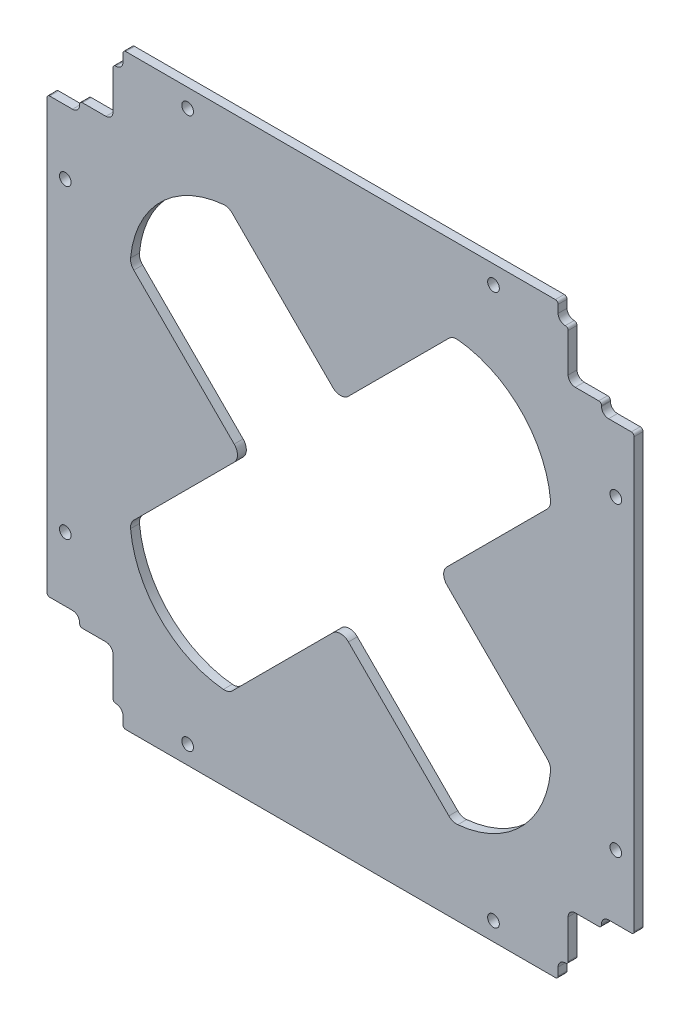
SolidWorks part; units mm, degrees
material "FR4_stuffedProtoboard"
ref_plane "Front Plane" through (0, 0, 0) normal (0, 0, 1) x (1, 0, 0)
ref_plane "Top Plane" through (0, 0, 0) normal (0, 1, 0) x (1, 0, 0)
ref_plane "Right Plane" through (0, 0, 0) normal (1, 0, 0) x (0, 0, -1)
sketch "Sketch1" plane through (0, 0, 0) normal (0, 0, 1) x (1, 0, 0)
  line L0 (53, 53) -> (-53, -53) construction
  line L1 (53, 53) -> (-53, 53)
  line L2 (53, 53) -> (53, -53)
  line L3 (53, -53) -> (-53, -53)
  line L4 (-53, 53) -> (-53, -53)
  point P4 (0, 0)
  dimension "D1" = 106
  dimension "D2" = 106
extrude "mainOutline" add sketch "Sketch1" along normal blind 1.6
sketch "axisLabels" plane through (0, 0, 0) normal (0, 0, -1) x (-1, 0, 0)
  text T0 "+Y"
  text T1 "+X"
sketch "Sketch4" plane through (0, 0, 0) normal (0, 0, -1) x (-1, 0, 0)
  line L10 (-53, 53) -> (53, 53) construction
  line L29 (41.3, 53) -> (41.3, 41.3)
  line L31 (53, 41.3) -> (41.3, 41.3)
  line L46 (53, 53) -> (53, -53) construction
  line L51 (53, 41.3) -> (53, 53)
  line L52 (53, 53) -> (41.3, 53)
  dimension "D11" = 11.7
  dimension "D12" = 11.7
extrude "railCutouts" cut sketch "Sketch4" against normal through all
sketch "Sketch13" plane through (0, 0, 0) normal (0, 0, -1) x (-1, 0, 0)
  line L0 (47.3, 39.4) -> (47.3, 41.3)
  line L2 (53, 41.3) -> (53, 39.4)
  line L5 (41.3, 53) -> (39.5, 53)
  line L6 (41.3, 53) -> (41.3, 50)
  line L7 (41.3, 50) -> (39.5, 50)
  line L8 (39.5, 53) -> (39.5, 50)
  line L9 (53, 41.3) -> (53, -53) construction
  line L10 (53, 41.3) -> (47.3, 41.3)
  line L12 (53, 39.4) -> (47.3, 39.4)
  line L13 (41.3, 41.3) -> (53, 41.3) construction
  dimension "D1" = 5.7
  dimension "D3" = 1.9
  dimension "D5" = 1.8
  dimension "D6" = 3
extrude "filletCutouts" cut sketch "Sketch13" against normal through all both and the other way through all
sketch "Sketch5" plane through (0, 0, 0) normal (0, 0, -1) x (-1, 0, 0)
  line L23 (42.198, 42.198) -> (45.4803, 45.4803) construction
  line L24 (41.3, 43.0961) -> (44.5823, 46.3784)
  line L25 (43.0961, 41.3) -> (46.3784, 44.5823)
  line L41 (41.3, 50) -> (41.3, 41.3) construction
  arc A14 (41.3, 43.0961) -> (43.0961, 41.3) centre (42.198, 42.198) ccw
  arc A15 (46.3784, 44.5823) -> (44.5823, 46.3784) centre (45.4803, 45.4803) ccw
  point P0 (41.3, 41.3)
  point P52 (43.8392, 43.8392)
  dimension "D14" = 1.27
  dimension "D7" = 45
extrude "dogbone" [suppressed] cut sketch "Sketch5" against normal through all
sketch "Sketch14" plane through (0, 0, 1.6) normal (0, 0, 1) x (1, 0, 0)
  point P1 (-47.3, 39.4)
sketch "Sketch27" plane through (0, 0, 1.6) normal (0, 0, 1) x (1, 0, 0)
  line L0 (-40.928, 42.198) -> (-40.928, 49.628)
  line L1 (-48.198, 39.028) -> (-53, 39.028)
  line L2 (-53, 39.4) -> (-53, -53) construction
  line L3 (-53, 39.028) -> (-53, 53)
  line L4 (-53, 53) -> (-39.128, 53)
  line L5 (-39.128, 53) -> (-39.128, 50.898)
  line L6 (-40.928, 49.628) -> (-40.398, 49.628)
  line L7 (-42.198, 40.928) -> (-46.928, 40.928)
  line L8 (-46.928, 40.928) -> (-46.928, 40.298)
  line L10 (53, 53) -> (-39.5, 53) construction
  arc A0 (-42.198, 40.928) -> (-40.928, 42.198) centre (-42.198, 42.198) ccw
  arc A1 (-40.398, 49.628) -> (-39.128, 50.898) centre (-40.398, 50.898) ccw
  arc A2 (-48.198, 39.028) -> (-46.928, 40.298) centre (-48.198, 40.298) ccw
  dimension "D1" = 1.27
extrude "smoothCorner" cut sketch "Sketch27" against normal blind 10
pattern_sketch "Sketch-Pattern1" [suppressed] of bodies 103 driven by "Sketch14"
mirror "Mirror1" about plane through (0, 0, 0) normal (1, 0, 0) of "smoothCorner", "filletCutouts", "railCutouts"
mirror "Mirror2" about plane through (0, 0, 0) normal (0, 1, 0) of "Mirror1"
fillet "Fillet1" [suppressed] radius 0.5
fillet "Fillet10" radius 0.5 8 edges at (46.928, -40.928, 0.8) (40.928, -49.628, 0.8) (40.928, 49.628, 0.8) (46.928, 40.928, 0.8) (-46.928, 40.928, 0.8) (-40.928, 49.628, 0.8) (-46.928, -40.928, 0.8) (-40.928, -49.628, 0.8)
sketch "Sketch6" [suppressed] plane through (0, 0, 0) normal (0, 0, -1) x (-1, 0, 0)
  line L0 (-39, 50) -> (-39, 53) construction
  line L1 (-39, 49) -> (-39, 53) construction
  line L2 (-53, 53) -> (41.3, 53) construction
  line L3 (-40, 50) -> (-40, 53)
  line L4 (-38, 50) -> (-38, 53)
  line L5 (-49, 39) -> (-53, 39) construction
  line L6 (-53, 39) -> (-48, 39) construction
  line L7 (-49, 38) -> (-53, 38)
  line L8 (-49, 40) -> (-53, 40)
  line L9 (-49, -39) -> (-55.2142, -39) construction
  line L10 (-48, -39) -> (-53, -39) construction
  line L11 (-49, -40) -> (-55.2142, -40)
  line L12 (-49, -38) -> (-55.2142, -38)
  line L13 (-39, -50) -> (-39, -53.9161) construction
  line L14 (-39, -53) -> (-39, -49) construction
  line L15 (-38, -50) -> (-38, -53.9161)
  line L16 (-40, -50) -> (-40, -53.9161)
  line L17 (39, -50.9) -> (39, -54.538) construction
  line L18 (39, -49.9) -> (39, -53) construction
  line L19 (40, -50.9) -> (40, -54.538)
  line L20 (38, -50.9) -> (38, -54.538)
  line L21 (49, -40.5) -> (54.2026, -40.5) construction
  line L22 (53, -40.5) -> (48, -40.5) construction
  line L23 (49, -39.5) -> (54.2026, -39.5)
  line L24 (49, -41.5) -> (54.2026, -41.5)
  line L25 (49, 40.5) -> (54.5566, 40.5) construction
  line L26 (48, 40.5) -> (53, 40.5) construction
  line L27 (49, 41.5) -> (54.5566, 41.5)
  line L28 (49, 39.5) -> (54.5566, 39.5)
  line L29 (39, 50.9) -> (39, 55.8281) construction
  line L30 (39, 53) -> (39, 49.9) construction
  line L31 (38, 50.9) -> (38, 55.8281)
  line L32 (40, 50.9) -> (40, 55.8281)
  line L33 (-48, -41.4) -> (-48, -39) construction
  line L34 (-39, -49) -> (-41.4, -49) construction
  line L35 (41.4, -49.9) -> (39, -49.9) construction
  line L36 (48, -40.5) -> (48, -41.4) construction
  line L37 (48, 41.4) -> (48, 40.5) construction
  line L38 (39, 49.9) -> (41.4, 49.9) construction
  arc A0 (-40, 50) -> (-38, 50) centre (-39, 50) ccw
  arc A1 (-38, 53) -> (-40, 53) centre (-39, 53) ccw
  arc A2 (-49, 38) -> (-49, 40) centre (-49, 39) ccw
  arc A3 (-53, 40) -> (-53, 38) centre (-53, 39) ccw
  arc A4 (-49, -40) -> (-49, -38) centre (-49, -39) ccw
  arc A5 (-55.2142, -38) -> (-55.2142, -40) centre (-55.2142, -39) ccw
  arc A6 (-38, -50) -> (-40, -50) centre (-39, -50) ccw
  arc A7 (-40, -53.9161) -> (-38, -53.9161) centre (-39, -53.9161) ccw
  arc A8 (40, -50.9) -> (38, -50.9) centre (39, -50.9) ccw
  arc A9 (38, -54.538) -> (40, -54.538) centre (39, -54.538) ccw
  arc A10 (49, -39.5) -> (49, -41.5) centre (49, -40.5) ccw
  arc A11 (54.2026, -41.5) -> (54.2026, -39.5) centre (54.2026, -40.5) ccw
  arc A12 (49, 41.5) -> (49, 39.5) centre (49, 40.5) ccw
  arc A13 (54.5566, 39.5) -> (54.5566, 41.5) centre (54.5566, 40.5) ccw
  arc A14 (38, 50.9) -> (40, 50.9) centre (39, 50.9) ccw
  arc A15 (40, 55.8281) -> (38, 55.8281) centre (39, 55.8281) ccw
  point P6 (-39, 51.5)
  point P11 (-51, 39)
  point P21 (-52.1071, -39)
  point P30 (-39, -51.958)
  point P39 (39, -52.719)
  point P48 (51.6013, -40.5)
  point P57 (51.7783, 40.5)
  point P66 (39, 53.364)
  point P75 (-39, 49)
  dimension "D1" = 1
extrude "solarFillets" [suppressed] cut sketch "Sketch6" against normal through all
fillet "handlingFillets" [suppressed] radius 1
sketch "Sketch7" plane through (0, 0, 1.6) normal (0, 0, 1) x (1, 0, 0)
  line L0 (-39.128, -53) -> (39.128, -53) construction
  line L1 (-53, 39.028) -> (-53, -39.028) construction
  line L2 (39.128, 53) -> (-39.128, 53) construction
  line L3 (-31.37, 28.67) -> (-31.37, 31.21) construction
  line L4 (-31.37, 31.21) -> (-28.83, 31.21) construction
  line L5 (-28.83, 31.21) -> (-28.83, 28.67) construction
  line L6 (-28.83, 28.67) -> (-31.37, 28.67) construction
  line L7 (-31.37, 28.67) -> (-28.83, 31.21) construction
  circle A1 centre (-28.4723, -17.925) radius 0.8
  circle A3 centre (-28.4723, -33.775) radius 0.8
  circle A5 centre (-31.37, 28.67) radius 0.425
  circle A7 centre (-28.83, 28.67) radius 0.425
  circle A9 centre (-30.1, 29.94) radius 0.425
  circle A10 centre (-28.83, 31.21) radius 0.425
  circle A11 centre (-31.37, 31.21) radius 0.425
  circle A12 centre (-31.37, 21.27) radius 0.425
  circle A13 centre (-28.83, 21.27) radius 0.425
  circle A14 centre (-30.1, 22.54) radius 0.425
  circle A15 centre (-28.83, 23.81) radius 0.425
  circle A16 centre (-31.37, 23.81) radius 0.425
  circle A17 centre (-31.37, 13.87) radius 0.425
  circle A18 centre (-28.83, 13.87) radius 0.425
  circle A19 centre (-30.1, 15.14) radius 0.425
  circle A20 centre (-28.83, 16.41) radius 0.425
  circle A21 centre (-31.37, 16.41) radius 0.425
  point P13 (-30.1, 29.94)
  dimension "D8" = 1.6
  dimension "D9" = 3
  dimension "D6" = 0.85
  dimension "D1" = 19.225
  dimension "D2" = 24.5277
  dimension "D3" = 15.85
  dimension "D4" = 23.06
  dimension "D5" = 22.9
  dimension "D7" = 2.54
  dimension "D10" = 7.4
extrude "connectorHoles" [suppressed] cut sketch "Sketch7" against normal through all
hole_wizard "M2 Clearance Hole1" positions "Sketch8" profile "Sketch9" hole size "M2" standard "ANSI Metric" end condition through all
sketch "Sketch8" plane through (0, 0, 0) normal (0, 0, -1) x (-1, 0, 0)
  line L0 (53, 39.028) -> (53, -39.028) construction
  line L1 (39.128, -53) -> (-39.128, -53) construction
  line L2 (-53, -39.028) -> (-53, 39.028) construction
  line L3 (53, 0) -> (-53, 0) construction
  line L5 (0, -53) -> (0, -11.6379) construction
  line L6 (53, 39.028) -> (53, -39.028) construction
  point P0 (49.5, -27.5)
  point P1 (27.5, -49.5)
  point P5 (-49.5, -27.5)
  point P30 (-27.5, -49.5)
  point P31 (-27.5, 49.5)
  point P32 (-49.5, 27.5)
  point P33 (27.5, 49.5)
  point P34 (49.5, 27.5)
  dimension "D1" = 3.5
  dimension "D2" = 3.5
  dimension "D3" = 55
  dimension "D4" = 3.5
  dimension "D5" = 55
  dimension "D6" = 55
sketch "Sketch9" plane through (-49.5, -27.5, 0) normal (1, 0, 0) x (0, 1, 0)
  line L0 (0, 0) -> (0, 1.6)
  line L1 (0, 1.6) -> (1.05, 1.6)
  line L2 (1.05, 1.6) -> (1.05, 0)
  line L5 (1.05, 0) -> (0, 0)
  line L11 (0, -6.35) -> (0, 107.95) construction
  dimension "Thru Hole Dia." = 2.1
  dimension "Thru Hole Depth" = 1.6
sketch "Sketch12" plane through (0, 0, 1.6) normal (0, 0, 1) x (1, 0, 0)
  line L1 (-39.128, -53) -> (39.128, -53) construction
  line L2 (53, -39.028) -> (53, 39.028) construction
  circle A0 centre (27.815, -42.5) radius 0.8
  circle A1 centre (38.585, -42.5) radius 0.8
  dimension "D1" = 1.6
  dimension "D2" = 10.77
  dimension "D3" = 10.5
  dimension "D4" = 25.185
extrude "interboardConnectorHoles" [suppressed] cut sketch "Sketch12" against normal through all both and the other way through all
sketch "Sketch17" [suppressed] plane through (0, 0, 1.6) normal (0, 0, 1) x (1, 0, 0)
  line L1 (-35.8, -40) -> (-21.8, -40)
  line L2 (-35.8, -40) -> (-35.8, -45)
  line L3 (-35.8, -45) -> (-21.8, -45)
  line L4 (-21.8, -40) -> (-21.8, -45)
  line L5 (-41.3, -50) -> (-41.3, -43.2836) construction
  line L6 (-38.9, -53) -> (38.9, -53) construction
  dimension "D1" = 8
  dimension "D2" = 13
  dimension "D3" = 19.5
  dimension "D4" = 14
  dimension "D5" = 5.5
extrude "Cut-Extrude7" [suppressed] cut sketch "Sketch17" against normal through all both and the other way through all
fillet "Fillet2" [suppressed] radius 1.27
sketch "Sketch11" [suppressed] plane through (0, 0, 0) normal (0, 0, -1) x (-1, 0, 0)
  circle A0 centre (0, 0) radius 36
  dimension "D1" = 72
extrude "Cut-Extrude2" [suppressed] cut sketch "Sketch11" against normal through all both and the other way through all
sketch "Sketch15" plane through (0, 0, 0) normal (0, 0, -1) x (-1, 0, 0)
  line L0 (-39.128, 53) -> (39.128, 53) construction
  line L1 (45, 53) -> (-45, 53)
  line L2 (45, 53) -> (45, 46.8)
  line L3 (45, 46.8) -> (-45, 46.8)
  line L4 (-45, 53) -> (-45, 46.8)
  line L5 (45, -53) -> (-45, -53)
  line L6 (45, -53) -> (45, -46.8)
  line L7 (45, -46.8) -> (-45, -46.8)
  line L8 (-45, -53) -> (-45, -46.8)
  line L9 (39.128, -53) -> (-39.128, -53) construction
  line L10 (-53, -39.028) -> (-53, 39.028) construction
  line L11 (-53, 45) -> (-47.8, 45)
  line L12 (-53, 45) -> (-53, -45)
  line L13 (-53, -45) -> (-47.8, -45)
  line L14 (-47.8, 45) -> (-47.8, -45)
  line L15 (53, 45) -> (47.8, 45)
  line L16 (53, 45) -> (53, -45)
  line L17 (53, -45) -> (47.8, -45)
  line L18 (47.8, 45) -> (47.8, -45)
  line L19 (53, 39.028) -> (53, -39.028) construction
  point P8 (0, 53)
  point P11 (0, -53)
  point P22 (-53, 0)
  point P25 (53, 0)
  dimension "D1" = 90
  dimension "D3" = 6.2
  dimension "D5" = 5.2
extrude "Cut-Extrude5" cut sketch "Sketch15" against normal blind 0.001
sketch "Sketch18" [suppressed] plane through (0, 0, 1.6) normal (0, 0, 1) x (1, 0, 0)
  line L0 (-43.2836, -41.3) -> (-46.4, -41.3) construction
  line L1 (-44.8418, -41.3) -> (-41.3, -41.3)
  line L2 (-44.8418, -41.3) -> (-44.8418, -36.3)
  line L3 (-44.8418, -36.3) -> (-41.3, -36.3)
  line L4 (-41.3, -41.3) -> (-41.3, -36.3)
  line L5 (-41.3, -50) -> (-41.3, -43.2836) construction
  dimension "D1" = 5
extrude "Boss-Extrude1" [suppressed] add sketch "Sketch18" against normal up to surface (1.6 mm away) up to face at (0, 0, 0)
sketch "Sketch16" [suppressed] plane through (0, 0, 1.6) normal (0, 0, 1) x (1, 0, 0)
  line L4 (-45, -53) -> (45, -53)
  line L5 (45, -53) -> (45, -46.8)
  line L6 (45, -46.8) -> (-45, -46.8)
  line L7 (-45, -46.8) -> (-45, -53)
  line L8 (-45, -53) -> (45, -53)
  line L9 (45, -53) -> (45, -46.8)
  line L10 (45, -46.8) -> (-45, -46.8)
  line L11 (-45, -46.8) -> (-45, -53)
  line L12 (45, 53) -> (-45, 53)
  line L13 (45, 46.8) -> (45, 53)
  line L14 (-45, 46.8) -> (45, 46.8)
  line L15 (-45, 53) -> (-45, 46.8)
  line L16 (45, 53) -> (-45, 53)
  line L17 (45, 46.8) -> (45, 53)
  line L18 (-45, 46.8) -> (45, 46.8)
  line L19 (-45, 53) -> (-45, 46.8)
  line L20 (-47.8, 45) -> (-53, 45)
  line L21 (-53, 45) -> (-53, -45)
  line L22 (-53, -45) -> (-47.8, -45)
  line L23 (-47.8, -45) -> (-47.8, 45)
  line L24 (-47.8, 45) -> (-53, 45)
  line L25 (-53, 45) -> (-53, -45)
  line L26 (-53, -45) -> (-47.8, -45)
  line L27 (-47.8, -45) -> (-47.8, 45)
  line L28 (53, 45) -> (47.8, 45)
  line L29 (47.8, 45) -> (47.8, -45)
  line L30 (47.8, -45) -> (53, -45)
  line L31 (53, -45) -> (53, 45)
  line L32 (53, 45) -> (47.8, 45)
  line L33 (47.8, 45) -> (47.8, -45)
  line L34 (47.8, -45) -> (53, -45)
  line L35 (53, -45) -> (53, 45)
  dimension "D1" = 0
  dimension "D2" = 0
  dimension "D3" = 0
  dimension "D4" = 0
extrude "Cut-Extrude6" [suppressed] cut sketch "Sketch16" against normal blind 0.001
sketch "Sketch19" plane through (0, 0, 0) normal (0, 0, 1) x (1, 0, 0)
  line L50 (14, -4) -> (6, -4) construction
  line L51 (32, -13.5731) -> (32, -10.1269) construction
  line L54 (0, -16.7) -> (0, -7) construction
  line L55 (6, -19.7) -> (14, -19.7) construction
  line L80 (14, -4) -> (6, -4) construction
  line L81 (32, -13.5731) -> (32, -10.1269) construction
  line L89 (0, -16.7) -> (0, -7) construction
  line L90 (6, -19.7) -> (14, -19.7) construction
  line L91 (0, -4) -> (36, -4)
  line L92 (0, -4) -> (0, -19.7)
  line L93 (0, -19.7) -> (36, -19.7)
  line L106 (-1, -3) -> (-1, -20.7)
  line L107 (-1, -20.7) -> (36.6053, -20.7)
  line L108 (-1, -3) -> (36.6053, -3)
  line L109 (-3, 1) -> (-20.7, 1)
  line L110 (-3, 1) -> (-3, -36.6053)
  line L111 (-20.7, 1) -> (-20.7, -36.6053)
  line L112 (1, 3) -> (1, 20.7)
  line L113 (1, 3) -> (-36.6053, 3)
  line L114 (1, 20.7) -> (-36.6053, 20.7)
  line L115 (3, -1) -> (20.7, -1)
  line L116 (3, -1) -> (3, 36.6053)
  line L117 (20.7, -1) -> (20.7, 36.6053)
  arc A9 (36, -4) -> (36, -19.7) centre (20.3594, -11.85) cw
  arc A13 (36.6053, -3) -> (36.6053, -20.7) centre (20.3594, -11.85) cw
  arc A14 (-3, -36.6053) -> (-20.7, -36.6053) centre (-11.85, -20.3594) cw
  arc A15 (-36.6053, 3) -> (-36.6053, 20.7) centre (-20.3594, 11.85) cw
  arc A16 (3, 36.6053) -> (20.7, 36.6053) centre (11.85, 20.3594) cw
  dimension "D1" = 17.5
  dimension "D2" = 36
  dimension "D3" = 1
  dimension "D4" = 4
sketch "Sketch21" plane through (0, 0, 0) normal (0, 0, 1) x (1, 0, 0)
  circle A0 centre (0, 0) radius 22.5
  dimension "D1" = 45
extrude "Cut-Extrude10" [suppressed] cut sketch "Sketch21" against normal through all and the other way through all
sketch "Sketch22" [suppressed] plane through (0, 0, 1.6) normal (0, 0, 1) x (1, 0, 0)
  line L0 (21.5668, -46.3155) -> (46.3155, -21.5668)
  line L1 (38.5373, -13.7886) -> (46.3155, -21.5668) construction
  line L2 (21.5668, -46.3155) -> (-12.3744, -12.3744)
  line L3 (13.7886, -38.5373) -> (38.5373, -13.7886) construction
  line L4 (13.7886, -38.5373) -> (38.5373, -13.7886) construction
  line L5 (-12.3744, -12.3744) -> (12.3744, 12.3744)
  line L6 (12.3744, 12.3744) -> (46.3155, -21.5668)
  dimension "D1" = 11
extrude "Cut-Extrude11" [suppressed] cut sketch "Sketch22" against normal through all both and the other way through all
fillet "Fillet4" [suppressed] radius 2
extrude "1U pinwheel turnstile cutout" [suppressed] cut sketch "Sketch19" along normal up to next contours L111 A14 L110 L109 | L107 A13 L108 L106 | L116 A16 L117 L115 | L112 L114 A15 L113
sketch "Sketch26" plane through (0, 0, 1.6) normal (0, 0, 1) x (1, 0, 0)
  line L0 (-16.2988, 0) -> (-36.8049, 20.5061) construction
  line L1 (0, 16.2988) -> (-7.7782, 24.077) construction
  line L2 (-24.077, 7.7782) -> (-16.2988, 0) construction
  line L3 (0, 16.2988) -> (-7.7782, 24.077) construction
  line L4 (-24.077, 7.7782) -> (-16.2988, 0) construction
  line L5 (-20.5061, 36.8049) -> (0, 16.2988) construction
  line L6 (36.8049, 20.5061) -> (16.2988, 0) construction
  line L7 (0, 16.2988) -> (20.5061, 36.8049) construction
  line L8 (20.5061, -36.8049) -> (0, -16.2988) construction
  line L9 (16.2988, 0) -> (36.8049, -20.5061) construction
  line L10 (-36.8049, -20.5061) -> (-16.2988, 0) construction
  line L11 (0, -16.2988) -> (-20.5061, -36.8049) construction
  line L12 (-17.713, 0) -> (-37.8275, 20.1145)
  line L13 (-20.1145, 37.8275) -> (0, 17.713)
  line L14 (0, 17.713) -> (20.1145, 37.8275)
  line L15 (37.8275, 20.1145) -> (17.713, 0)
  line L16 (17.713, 0) -> (37.8275, -20.1145)
  line L17 (20.1145, -37.8275) -> (0, -17.713)
  line L18 (0, -17.713) -> (-20.1145, -37.8275)
  line L19 (-37.8275, -20.1145) -> (-17.713, 0)
  arc A0 (-17.1196, 32.4741) -> (-32.4741, 17.1196) centre (-16.2012, 16.2012) ccw construction
  arc A1 (-17.1196, 32.4741) -> (-32.4741, 17.1196) centre (-16.2012, 16.2012) ccw construction
  arc A2 (-36.8049, 20.5061) -> (-20.5061, 36.8049) centre (-19.3436, 19.3436) cw construction
  arc A3 (20.5061, 36.8049) -> (36.8049, 20.5061) centre (19.3436, 19.3436) cw construction
  arc A4 (36.8049, -20.5061) -> (20.5061, -36.8049) centre (19.3436, -19.3436) cw construction
  arc A5 (-20.5061, -36.8049) -> (-36.8049, -20.5061) centre (-19.3436, -19.3436) cw construction
  arc A6 (-37.8275, 20.1145) -> (-20.1145, 37.8275) centre (-19.3436, 19.3436) cw
  arc A7 (20.1145, 37.8275) -> (37.8275, 20.1145) centre (19.3436, 19.3436) cw
  arc A8 (37.8275, -20.1145) -> (20.1145, -37.8275) centre (19.3436, -19.3436) cw
  arc A9 (-20.1145, -37.8275) -> (-37.8275, -20.1145) centre (-19.3436, -19.3436) cw
  dimension "D1" = 17.5
  dimension "D3" = 4
  dimension "D2" = 29
  dimension "D4" = 1
extrude "1I circular turnstile cutout" cut sketch "Sketch26" against normal blind 10
sketch "Sketch25" [suppressed] plane through (0, 0, 0) normal (0, 0, -1) x (-1, 0, 0)
  line L0 (36.332, -29.0597) -> (36.332, -25.6135) construction
  line L1 (10.332, -35.1866) -> (18.332, -35.1866) construction
  line L2 (18.332, -19.4866) -> (10.332, -19.4866) construction
  line L3 (4.332, -32.1866) -> (4.332, -22.4866) construction
  line L4 (36.332, -29.0597) -> (36.332, -25.6135) construction
  line L5 (10.332, -35.1866) -> (18.332, -35.1866) construction
  line L6 (18.332, -19.4866) -> (10.332, -19.4866) construction
  line L7 (4.332, -32.1866) -> (4.332, -22.4866) construction
  line L8 (40.332, -35.1866) -> (4.332, -35.1866) construction
  line L9 (4.332, -35.1866) -> (4.332, -19.4866) construction
  line L10 (4.332, -19.4866) -> (40.332, -19.4866) construction
  line L11 (40.9373, -36.1866) -> (3.332, -36.1866)
  line L12 (3.332, -36.1866) -> (3.332, -18.4866)
  line L13 (3.332, -18.4866) -> (40.9373, -18.4866)
  line L14 (-18.4866, -3.332) -> (-18.4866, -40.9373)
  line L15 (-36.1866, -3.332) -> (-18.4866, -3.332)
  line L16 (-36.1866, -40.9373) -> (-36.1866, -3.332)
  line L17 (-3.332, 18.4866) -> (-40.9373, 18.4866)
  line L18 (-3.332, 36.1866) -> (-3.332, 18.4866)
  line L19 (-40.9373, 36.1866) -> (-3.332, 36.1866)
  line L20 (18.4866, 3.332) -> (18.4866, 40.9373)
  line L21 (36.1866, 3.332) -> (18.4866, 3.332)
  line L22 (36.1866, 40.9373) -> (36.1866, 3.332)
  arc A0 (40.332, -19.4866) -> (40.332, -35.1866) centre (24.6914, -27.3366) cw construction
  arc A1 (40.9373, -18.4866) -> (40.9373, -36.1866) centre (24.6914, -27.3366) cw
  arc A2 (-18.4866, -40.9373) -> (-36.1866, -40.9373) centre (-27.3366, -24.6914) cw
  arc A3 (-40.9373, 18.4866) -> (-40.9373, 36.1866) centre (-24.6914, 27.3366) cw
  arc A4 (18.4866, 40.9373) -> (36.1866, 40.9373) centre (27.3366, 24.6914) cw
  dimension "D1" = 17.5
  dimension "D2" = 36
  dimension "D3" = 1
  dimension "D4" = 4
extrude "2U turnstile cutout" [suppressed] cut sketch "Sketch25" against normal up to next
sketch "Sketch23" [suppressed] plane through (0, 0, 1.6) normal (0, 0, 1) x (1, 0, 0)
  line L0 (-20.7, -36.6053) -> (-20.7, 1) construction
  line L1 (-20.7, -20.7) -> (20.7, -20.7)
  line L2 (-20.7, -20.7) -> (-20.7, 20.7)
  line L3 (-20.7, 20.7) -> (20.7, 20.7)
  line L4 (20.7, -20.7) -> (20.7, 20.7)
  line L5 (-36.6053, 20.7) -> (1, 20.7) construction
  line L6 (36.6053, -20.7) -> (-1, -20.7) construction
  line L7 (20.7, 36.6053) -> (20.7, -1) construction
extrude "Cut-Extrude16" [suppressed] cut sketch "Sketch23" against normal blind 10
fillet "Fillet5" [suppressed] radius 1
sketch "Sketch24" plane through (0, 0, 1.6) normal (0, 0, 1) x (1, 0, 0)
  line L0 (-53, -39.028) -> (-53, 39.028) construction
  line L1 (52.8, 52.8) -> (-52.8, 52.8)
  line L2 (52.8, 52.8) -> (52.8, -52.8)
  line L3 (52.8, -52.8) -> (-52.8, -52.8)
  line L4 (-52.8, 52.8) -> (-52.8, -52.8)
  line L5 (-39.128, 53) -> (39.128, 53) construction
  line L6 (53, 39.028) -> (53, -39.028) construction
  line L7 (39.128, -53) -> (-39.128, -53) construction
  dimension "D1" = 0.2
  dimension "D2" = 0.2
  dimension "D3" = 0.2
  dimension "D4" = 0.2
extrude "Cut-Extrude19" cut sketch "Sketch24" against normal through all flip side to cut
fillet "Fillet7" radius 0.5 8 edges at (-52.8, -39.028, 0.8005) (-39.128, -52.8, 0.8005) (39.128, -52.8, 0.8005) (52.8, -39.028, 0.8005) (52.8, 39.028, 0.8005) (39.128, 52.8, 0.8005) (-39.128, 52.8, 0.8005) (-52.8, 39.028, 0.8005)
fillet "Fillet8" [suppressed] radius 1
fillet "Fillet9" radius 2 12 edges at (0, -17.713, 0.8) (17.713, 0, 0.8) (-17.713, 0, 0.8) (0, 17.713, 0.8) (-37.8275, -20.1145, 0.8) (-20.1145, -37.8275, 0.8) (20.1145, -37.8275, 0.8) (37.8275, -20.1145, 0.8) (37.8275, 20.1145, 0.8) (20.1145, 37.8275, 0.8) (-37.8275, 20.1145, 0.8) (-20.1145, 37.8275, 0.8)
